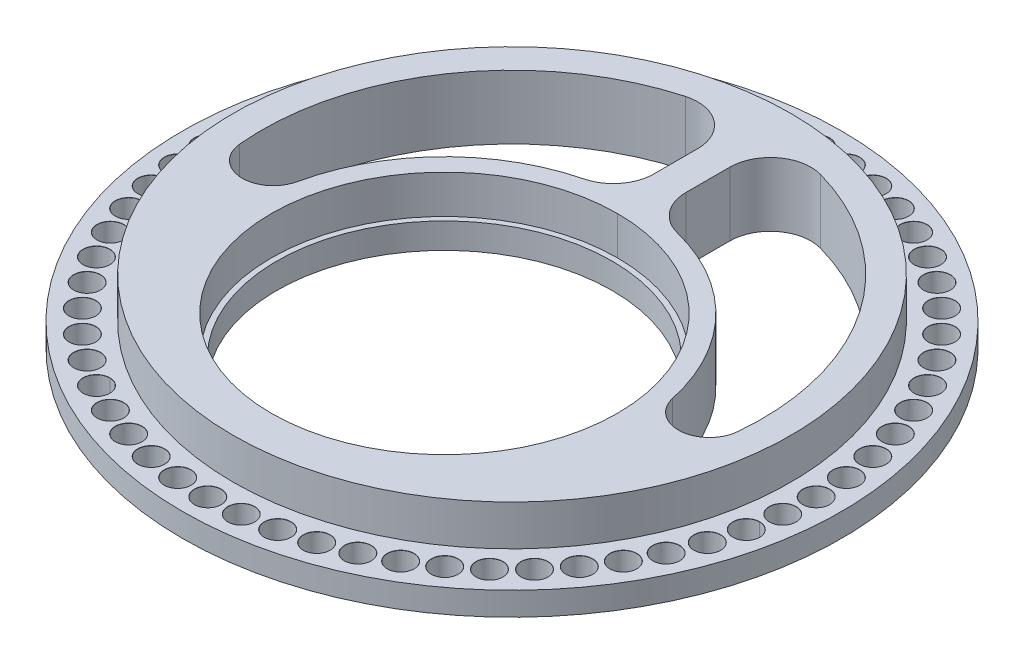
SolidWorks part; units mm, degrees
material "6061-T6 (SS)"
ref_plane "X-Y Datum" through (0, 0, 0) normal (0, 0, 1) x (1, 0, 0)
ref_plane "X-Z Datum" through (0, 0, 0) normal (0, 1, 0) x (1, 0, 0)
ref_plane "Y-Z Datum" through (0, 0, 0) normal (1, 0, 0) x (0, 0, -1)
sketch "Sketch1" plane through (0, 0, 0) normal (0, 1, 0) x (1, 0, 0)
  line L0 (0, 0) -> (0, -12.7) construction
  line L1 (0, -43.0151) -> (0, 43.0151) construction
  line L2 (0, 52.3875) -> (0, 61.9125) construction
  circle A0 centre (0, -12.7) radius 30.988
  circle A1 centre (0, 0) radius 52.3875 construction
  circle A2 centre (0, 0) radius 61.9125
  circle A3 centre (0, 0) radius 57.15 construction
  point P12 (0, 57.15)
  dimension "D2" = 61.976
  dimension "D3" = 104.775
  dimension "D4" = 123.825
  dimension "D5" = 114.3
  dimension "D1" = 12.7
extrude "Slotted-Body Extrude" add sketch "Sketch1" along normal blind 4.191 and the other way blind 0.2032
sketch "Sketch5" plane through (0, 4.191, 0) normal (0, 1, 0) x (1, 0, 0)
  circle A0 centre (0, 0) radius 52.3875 construction
  circle A1 centre (0, 0) radius 52.3875
extrude "Boss-Extrude3" add sketch "Sketch5" along normal blind 7.62
sketch "Sketch6" plane through (0, -0.2032, 0) normal (0, -1, 0) x (1, 0, 0)
  line L0 (0, -79.2756) -> (0, 0) construction
  line L2 (3.014, -37.9067) -> (3.014, -29.6741)
  line L4 (-3.014, -37.9067) -> (-3.014, -29.6741)
  circle A0 centre (0, 12.7) radius 30.988 construction
  circle A1 centre (0, 12.7) radius 30.988 construction
  circle A2 centre (0, 12.7) radius 32.512
  arc A9 (-35.2562, 5.0907) -> (-8.7792, -22.2832) centre (0, 12.7) ccw
  arc A10 (-46.783, 4.406) -> (-12.6921, -45.2435) centre (0, 0) ccw
  arc A11 (-46.783, 4.406) -> (-35.2562, 5.0907) centre (-40.9667, 3.8583) cw
  arc A19 (-3.014, -29.6741) -> (-8.7792, -22.2832) centre (-10.634, -29.6741) ccw
  arc A20 (-3.014, -37.9067) -> (-12.6921, -45.2435) centre (-10.634, -37.9067) cw
  circle A21 centre (0, 0) radius 61.9125 construction
  arc A27 (46.783, 4.406) -> (35.2562, 5.0907) centre (40.9667, 3.8583) ccw
  arc A28 (46.783, 4.406) -> (12.6921, -45.2435) centre (0, 0) cw
  arc A29 (3.014, -37.9067) -> (12.6921, -45.2435) centre (10.634, -37.9067) ccw
  arc A30 (3.014, -29.6741) -> (8.7792, -22.2832) centre (10.634, -29.6741) cw
  arc A31 (35.2562, 5.0907) -> (8.7792, -22.2832) centre (0, 12.7) cw
  point P30 (0, 0)
  point P31 (-3.014, -23.2419)
  point P32 (0, 0)
  point P36 (-3.014, -46.8932)
  dimension "D1" = 65.024
  dimension "D2" = 7.62
  dimension "D3" = 5.842
  dimension "D4" = 46.99
  dimension "D5" = 7.62
  dimension "D6" = 36.068
  dimension "D8" = 8.2326
extrude "Cut-Extrude5" cut sketch "Sketch6" against normal through all
sketch "Sketch8" plane through (0, -0.2032, 0) normal (0, -1, 0) x (1, 0, 0)
  circle A0 centre (0, 12.7) radius 32.512 construction
  circle A1 centre (0, 12.7) radius 32.512
  circle A2 centre (0, 12.7) radius 31.496
  dimension "D1" = 62.992
extrude "Boss-Extrude4" add sketch "Sketch8" against normal blind 4.795 separate body
hole_wizard "Ø5.0mm Dowel Hole2" positions "Sketch9" profile "Sketch10" hole size "Ø5.0" standard "ANSI Metric" end condition through all
sketch "Sketch9" plane through (0, 4.191, 0) normal (0, 1, 0) x (1, 0, 0)
  point P0 (0, 57.15)
sketch "Sketch10" plane through (0, 4.191, -57.15) normal (1, 0, 0) x (0, 0, 1)
  line L0 (0, 0) -> (0, 4.3942)
  line L1 (0, 4.3942) -> (2.5, 4.3942)
  line L2 (2.5, 4.3942) -> (2.5, 0.025)
  line L3 (2.5, 0.025) -> (2.525, 0)
  line L5 (2.525, 0) -> (0, 0)
  line L6 (-2.5, 0.025) -> (-2.525, 0) construction
  line L11 (0, -6.35) -> (0, 107.95) construction
  dimension "Thru Hole Dia." = 5
  dimension "Thru Hole Depth" = 4.3942
  dimension "Near C'Sink Dia." = 5.05
  dimension "Near C'Sink Angle" = 90
pattern_circular "CirPattern1" count 60 over 360 about axis through (0, 11.811, 0) along (0, -1, 0) of "Ø5.0mm Dowel Hole2"
ref_point "Point1"
ref_plane "Plane1" through (0, 0, 0) normal (1, 0, 0) x (0, 0, -1)
split line "Split Line1"
ref_point "Point2"
ref_point "Point3"
ref_point "Point4"
ref_point "Point5"
split line "Split Line2"
split line "Split Line3"
ref_plane "Plane2" through (-42.4707, 0, 0) normal (-1, 0, 0) x (0, 0, 1)
ref_plane "Plane3" through (55.9011, 0, 0) normal (-1, 0, 0) x (0, 0, 1)
split line "Split Line4"
split line "Split Line5"
sketch "Sketch17" plane through (0, 4.191, 0) normal (0, 1, 0) x (1, 0, 0)
  line L0 (-71.12, 66.6242) -> (71.12, 66.6242) construction
  line L1 (-71.12, -66.6242) -> (71.12, -66.6242) construction
  line L2 (-71.12, -66.6242) -> (-71.12, 66.6242) construction
  line L3 (-71.12, 66.6242) -> (71.12, 66.6242) construction
  line L4 (71.12, -66.6242) -> (71.12, 66.6242) construction
  line L5 (-71.12, -66.6242) -> (71.12, 66.6242) construction
  line L6 (-71.12, 66.6242) -> (-45.1836, 42.3273) construction
  line L7 (-71.12, 88.7603) -> (71.12, 88.7603)
  line L11 (-71.12, 59.8198) -> (-15.9607, 59.8198)
  line L12 (-71.12, 88.7603) -> (71.12, 88.7603)
  line L13 (-71.12, 88.7603) -> (-71.12, -66.6242)
  line L14 (-71.12, -66.6242) -> (71.12, -66.6242)
  line L15 (71.12, 88.7603) -> (71.12, -66.6242)
  line L16 (15.9607, 59.8198) -> (71.12, 59.8198)
  line L17 (0, 0) -> (71.12, -66.6242) construction
  arc A1 (15.9607, 59.8198) -> (-15.9607, 59.8198) centre (0, 0) ccw
  point P0 (0, 0)
  dimension "D1" = 142.24
  dimension "D2" = 133.2484
  dimension "D3" = 22.1361
sketch "Sketch13" plane through (0, 11.811, 0) normal (0, 1, 0) x (1, 0, 0)
  line L0 (3.014, 29.6741) -> (3.014, 37.9067) construction
  line L1 (-3.014, 37.9067) -> (-3.014, 29.6741) construction
  line L2 (3.014, 29.6741) -> (3.014, 37.9067) construction
  line L3 (-3.014, 37.9067) -> (-3.014, 29.6741) construction
  line L4 (-6.062, 37.9067) -> (-6.062, 29.6741)
  line L5 (6.062, 29.6741) -> (6.062, 37.9067)
  circle A0 centre (0, -12.7) radius 31.496 construction
  circle A1 centre (0, -12.7) radius 31.496 construction
  circle A2 centre (0, -12.7) radius 28.448
  arc A3 (35.2562, -5.0907) -> (46.783, -4.406) centre (40.9667, -3.8583) ccw construction
  arc A4 (35.2562, -5.0907) -> (8.7792, 22.2832) centre (0, -12.7) ccw construction
  arc A5 (3.014, 29.6741) -> (8.7792, 22.2832) centre (10.634, 29.6741) ccw construction
  arc A6 (46.783, -4.406) -> (12.6921, 45.2435) centre (0, 0) ccw construction
  arc A7 (12.6921, 45.2435) -> (3.014, 37.9067) centre (10.634, 37.9067) ccw construction
  arc A8 (-46.783, -4.406) -> (-35.2562, -5.0907) centre (-40.9667, -3.8583) ccw construction
  arc A9 (-8.7792, 22.2832) -> (-35.2562, -5.0907) centre (0, -12.7) ccw construction
  arc A10 (-8.7792, 22.2832) -> (-3.014, 29.6741) centre (-10.634, 29.6741) ccw construction
  arc A11 (-3.014, 37.9067) -> (-12.6921, 45.2435) centre (-10.634, 37.9067) ccw construction
  arc A12 (-12.6921, 45.2435) -> (-46.783, -4.406) centre (0, 0) ccw construction
  arc A13 (35.2562, -5.0907) -> (46.783, -4.406) centre (40.9667, -3.8583) ccw construction
  arc A14 (35.2562, -5.0907) -> (8.7792, 22.2832) centre (0, -12.7) ccw construction
  arc A15 (3.014, 29.6741) -> (8.7792, 22.2832) centre (10.634, 29.6741) ccw construction
  arc A16 (46.783, -4.406) -> (12.6921, 45.2435) centre (0, 0) ccw construction
  arc A17 (12.6921, 45.2435) -> (3.014, 37.9067) centre (10.634, 37.9067) ccw construction
  arc A18 (-46.783, -4.406) -> (-35.2562, -5.0907) centre (-40.9667, -3.8583) ccw construction
  arc A19 (-8.7792, 22.2832) -> (-35.2562, -5.0907) centre (0, -12.7) ccw construction
  arc A20 (-8.7792, 22.2832) -> (-3.014, 29.6741) centre (-10.634, 29.6741) ccw construction
  arc A21 (-3.014, 37.9067) -> (-12.6921, 45.2435) centre (-10.634, 37.9067) ccw construction
  arc A22 (-12.6921, 45.2435) -> (-46.783, -4.406) centre (0, 0) ccw construction
  arc A23 (-11.8689, 42.3087) -> (-43.7484, -4.1202) centre (0, 0) ccw
  arc A24 (-43.7484, -4.1202) -> (-38.2356, -4.4477) centre (-40.9667, -3.8583) ccw
  arc A25 (-9.5211, 25.2396) -> (-38.2356, -4.4477) centre (0, -12.7) ccw
  arc A26 (-9.5211, 25.2396) -> (-6.062, 29.6741) centre (-10.634, 29.6741) ccw
  arc A27 (-6.062, 37.9067) -> (-11.8689, 42.3087) centre (-10.634, 37.9067) ccw
  arc A28 (11.8689, 42.3087) -> (6.062, 37.9067) centre (10.634, 37.9067) ccw
  arc A29 (6.062, 29.6741) -> (9.5211, 25.2396) centre (10.634, 29.6741) ccw
  arc A30 (38.2356, -4.4477) -> (9.5211, 25.2396) centre (0, -12.7) ccw
  arc A31 (38.2356, -4.4477) -> (43.7484, -4.1202) centre (40.9667, -3.8583) ccw
  arc A32 (43.7484, -4.1202) -> (11.8689, 42.3087) centre (0, 0) ccw
  dimension "D1" = 3.048
  dimension "D2" = 3.048
sketch "Sketch11" plane through (0, -0.2032, 0) normal (0, -1, 0) x (1, 0, 0)
  line L1 (-61.9125, -61.9125) -> (61.9125, -61.9125)
  line L2 (-61.9125, -61.9125) -> (-61.9125, 61.9125)
  line L3 (-61.9125, 61.9125) -> (61.9125, 61.9125)
  line L4 (61.9125, -61.9125) -> (61.9125, 61.9125)
  line L5 (-61.9125, -61.9125) -> (61.9125, 61.9125) construction
  line L6 (-61.9125, 61.9125) -> (61.9125, -61.9125) construction
  circle A0 centre (0, 0) radius 61.9125 construction
  point P0 (0, 0)
sketch "Sketch14" plane through (0, 4.191, 0) normal (0, 1, 0) x (1, 0, 0)
  line L0 (-61.9125, 61.9125) -> (-61.9125, -61.9125) construction
  line L1 (-61.9125, 61.9125) -> (61.9125, 61.9125) construction
  line L2 (-61.9125, 61.9125) -> (-61.9125, -61.9125) construction
  line L3 (-61.9125, 61.9125) -> (61.9125, 61.9125) construction
  line L7 (-61.9125, -61.9125) -> (61.9125, 61.9125) construction
  line L8 (-61.9125, -61.9125) -> (61.9125, 61.9125)
  line L9 (0, -0.6085) -> (0, 49999.3915) construction
  circle A0 centre (0, 0) radius 61.9125 construction
  circle A2 centre (0, 0) radius 61.9125 construction
  arc A3 (-62.4462, 2.4493) -> (62.4462, 2.4493) centre (0, -0.6085) cw
  arc A4 (-62.4462, 2.4493) -> (-77.6194, 1.8864) centre (-70.0571, 2.822) cw
  arc A5 (0, 61.9125) -> (-3.7531, 76.0115) centre (-4.0041, 68.3957) ccw
  arc A6 (-77.6194, 1.8864) -> (-3.7531, 76.0115) centre (-26.007, 24.3209) cw
  arc A7 (2.4493, -62.4462) -> (1.8864, -77.6194) centre (2.822, -70.0571) ccw
  arc A8 (2.4493, -62.4462) -> (61.9125, 0) centre (-0.6085, 0) ccw
  arc A9 (61.9125, 0) -> (76.0115, -3.7531) centre (68.3957, -4.0041) cw
  arc A10 (1.8864, -77.6194) -> (76.0115, -3.7531) centre (24.3209, -26.007) ccw
  arc A11 (62.4462, 2.4493) -> (77.6194, 1.8864) centre (70.0571, 2.822) ccw
  arc A12 (0, 61.9125) -> (3.7531, 76.0115) centre (4.0041, 68.3957) cw
  arc A13 (77.6194, 1.8864) -> (3.7531, 76.0115) centre (26.007, 24.3209) ccw
  arc A14 (-2.4493, -62.4462) -> (-61.9125, 0) centre (0.6085, 0) cw
  arc A15 (-61.9125, 0) -> (-76.0115, -3.7531) centre (-68.3957, -4.0041) ccw
  arc A16 (-1.8864, -77.6194) -> (-76.0115, -3.7531) centre (-24.3209, -26.007) cw
  arc A17 (-2.4493, -62.4462) -> (-1.8864, -77.6194) centre (-2.822, -70.0571) cw
  point P13 (-61.9125, 0)
  dimension "D1" = 7.62
  dimension "D2" = 7.62
